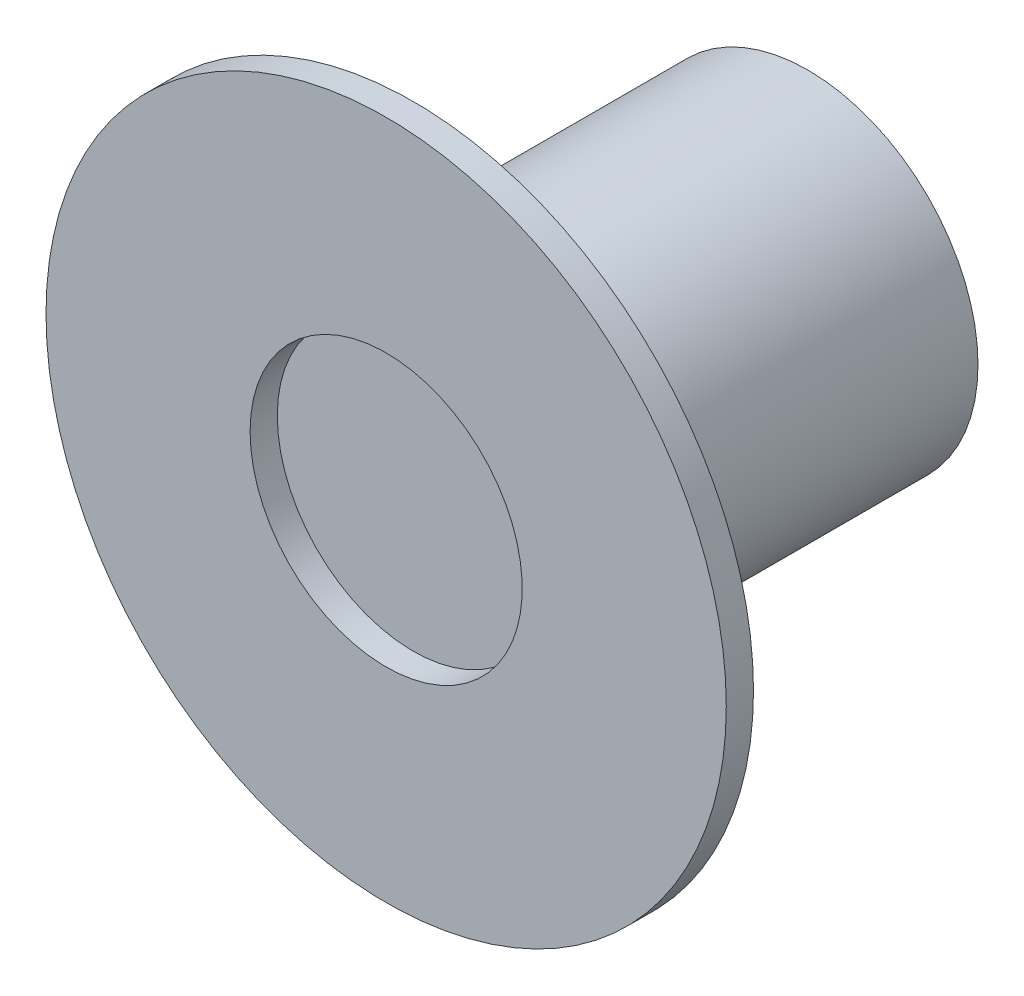
SolidWorks part; units mm, degrees
other "마크업1"
sketch "스케치14" plane through (30, 31, -30.5354) normal (0.2605, 0.9636, -0.0594) x (0.9655, -0.2601, 0.014)
sketch "스케치15" plane through (30, 31, -30.5354) normal (0.2605, 0.9636, -0.0594) x (0.9655, -0.2601, 0.014)
sketch "스케치16" plane through (30, 31, -30.5354) normal (0.2605, 0.9636, -0.0594) x (0.9655, -0.2601, 0.014)
sketch "스케치21" plane through (30, 31, -30.5354) normal (0.2605, 0.9636, -0.0594) x (0.9655, -0.2601, 0.014)
sketch "스케치23" plane through (30, 275, -27) normal (0.2605, 0.9636, -0.0594) x (0.9655, -0.2601, 0.014)
sketch "스케치28" plane through (20, 265, -24) normal (0.2605, 0.9636, -0.0594) x (0.9655, -0.2601, 0.014)
sketch "스케치31" plane through (20, 265, -24) normal (0.2605, 0.9636, -0.0594) x (0.9655, -0.2601, 0.014)
sketch "스케치32" plane through (20, 265, -23) normal (0.2605, 0.9636, -0.0594) x (0.9655, -0.2601, 0.014)
sketch "스케치33" plane through (20, 265, -23) normal (0.2605, 0.9636, -0.0594) x (0.9655, -0.2601, 0.014)
sketch "스케치38" plane through (25, 25, -31) normal (0.2605, 0.9636, -0.0594) x (0.9655, -0.2601, 0.014)
sketch "스케치39" plane through (25, 25, -31) normal (0.2605, 0.9636, -0.0594) x (0.9655, -0.2601, 0.014)
material "7075-T6 (SN)"
ref_plane "정면" through (0, 0, 0) normal (0, 0, 1) x (1, 0, 0)
ref_plane "윗면" through (0, 0, 0) normal (0, 1, 0) x (1, 0, 0)
ref_plane "우측면" through (0, 0, 0) normal (1, 0, 0) x (0, 0, -1)
sketch "스케치2" plane through (0, 6, 0) normal (0, 0, -1) x (1, 0, 0)
  circle A0 centre (0, 6) radius 10
  circle A1 centre (0, 6) radius 25
  dimension "D1" = 50
  dimension "30" = 20
extrude "보스-돌출2" add sketch "스케치2" along normal blind 2
sketch "스케치35" plane through (0, 0, -2) normal (0, 0, -1) x (-1, 0, 0)
  circle A0 centre (0, 0) radius 13.5
  dimension "D1" = 27
extrude "보스-돌출3" add sketch "스케치35" along normal blind 2
sketch "스케치36" plane through (0, 0, -4) normal (0, 0, -1) x (-1, 0, 0)
  circle A0 centre (0, 0) radius 12.5
  dimension "D1" = 25
extrude "보스-돌출4" add sketch "스케치36" along normal blind 27
sketch "스케치37" plane through (0, 0, -31) normal (0, 0, -1) x (-1, 0, 0)
  circle A0 centre (0, 0) radius 10
  dimension "D1" = 20
extrude "컷-돌출3" cut sketch "스케치37" against normal blind 3
